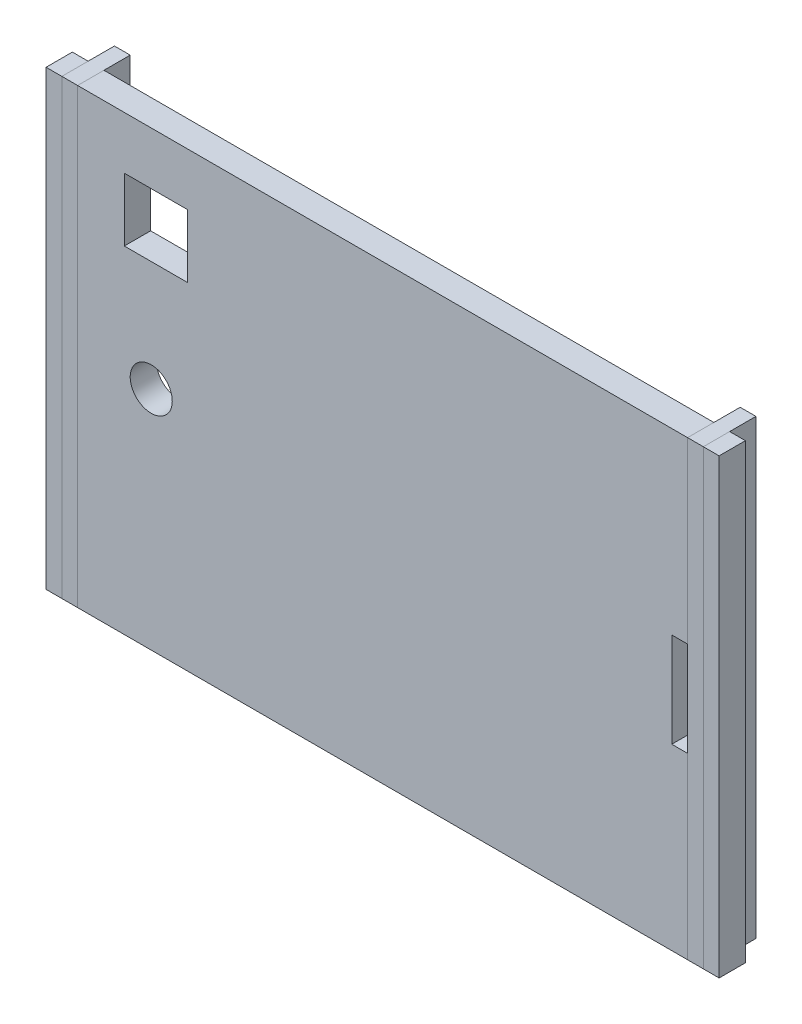
SolidWorks part; units mm, degrees
ref_plane "Спереди" through (0, 0, 0) normal (0, 0, 1) x (1, 0, 0)
ref_plane "Сверху" through (0, 0, 0) normal (0, 1, 0) x (1, 0, 0)
ref_plane "Справа" through (0, 0, 0) normal (1, 0, 0) x (0, 0, -1)
sketch "Эскиз1" plane through (0, 0, 0) normal (0, 0, 1) x (1, 0, 0)
  line L0 (-100.2463, 48.224) -> (-97.2463, 48.224)
  line L1 (-103.2463, 48.224) -> (24.7537, 48.224)
  line L2 (-103.2463, 48.224) -> (-103.2463, -37.776)
  line L3 (-103.2463, -37.776) -> (24.7537, -37.776)
  line L4 (24.7537, 48.224) -> (24.7537, -37.776)
  line L5 (-97.2463, 48.224) -> (-97.2463, -37.776)
  line L6 (-97.2463, -37.776) -> (-100.2463, -37.776)
  line L7 (-100.2463, -37.776) -> (-100.2463, 48.224)
  line L8 (21.7537, 48.224) -> (18.7537, 48.224)
  line L9 (18.7537, 48.224) -> (18.7537, -37.776)
  line L10 (18.7537, -37.776) -> (21.7537, -37.776)
  line L11 (21.7537, -37.776) -> (21.7537, 48.224)
  line L13 (15.7537, 14.224) -> (18.7537, 14.224)
  line L14 (15.7537, 14.224) -> (15.7537, -3.776)
  line L15 (15.7537, -3.776) -> (18.7537, -3.776)
  line L16 (18.7537, 14.224) -> (18.7537, -3.776)
  line L17 (-76.3639, 26.224) -> (-88.3639, 26.224)
  line L18 (-76.3639, 26.224) -> (-76.3639, 38.224)
  line L19 (-76.3639, 38.224) -> (-88.3639, 38.224)
  line L20 (-88.3639, 26.224) -> (-88.3639, 38.224)
  line L21 (-76.3639, 26.224) -> (-88.3639, 38.224) construction
  line L22 (-76.3639, 38.224) -> (-88.3639, 26.224) construction
  circle A0 centre (-83.2463, 5.224) radius 4
  point P16 (17.2537, -3.776)
  point P19 (-82.3639, 32.224)
  dimension "D11" = 8
  dimension "D1" = 86
  dimension "D2" = 128
  dimension "D3" = 3
  dimension "D4" = 3
  dimension "D5" = 3
  dimension "D6" = 3
  dimension "D7" = 3
  dimension "D8" = 18
  dimension "D9" = 34
  dimension "D10" = 0
  dimension "D12" = 14
  dimension "D13" = 43
  dimension "D14" = 12
  dimension "D15" = 12
  dimension "D16" = 10
extrude "Бобышка-Вытянуть1" add sketch "Эскиз1" against normal blind 5 contours L15 L14 L13 L9 L1 L5 L3 A0 L17 L20 L19 L18 | L3 L7 L1 L2 | L11 L3 L4 L1 region at (-101.7463, 5.224, 0) region at (-38.6943, 4.8243, 0) region at (23.2537, 5.224, 0)
extrude "Бобышка-Вытянуть3" add sketch "Эскиз1<5>" against normal blind 10 separate body contours L7 L3 L5 L0 | L3 L11 L1 L9 region at (-98.7463, 5.224, 0) region at (20.2537, 5.224, 0)
sketch "Эскиз1<5>" plane through (0, 0, 0) normal (0, 0, 1) x (1, 0, 0) same geometry as "Эскиз1"
